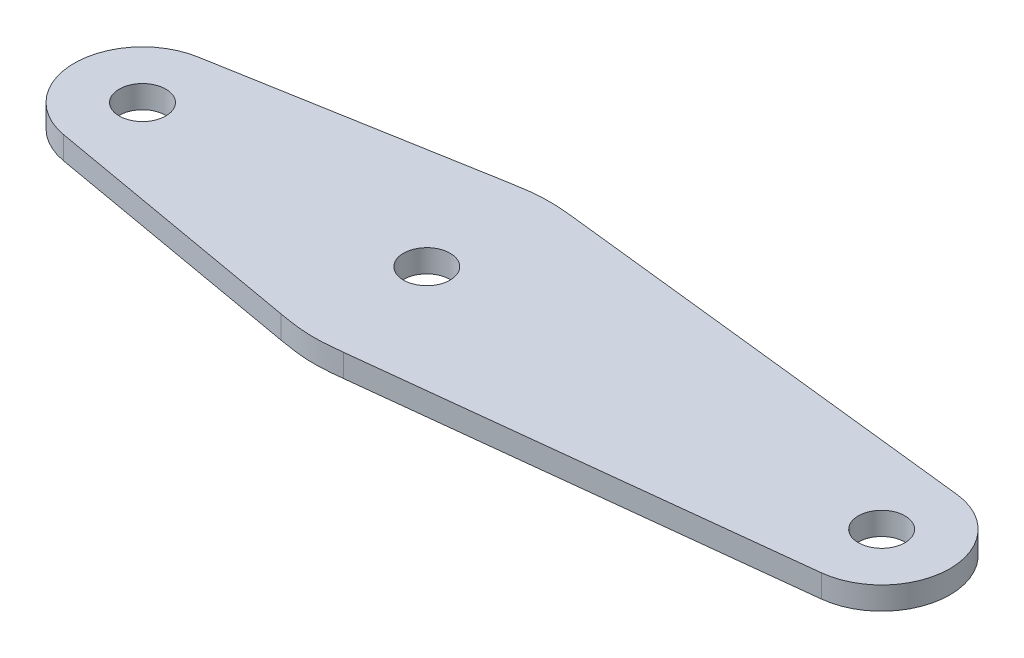
SolidWorks part; units mm, degrees
material "ABS"
ref_plane "前视基准面" through (0, 0, 0) normal (0, 0, 1) x (1, 0, 0)
ref_plane "上视基准面" through (0, 0, 0) normal (0, 1, 0) x (1, 0, 0)
ref_plane "右视基准面" through (0, 0, 0) normal (1, 0, 0) x (0, 0, -1)
other "Configuration Table"
sketch "草图1" plane through (0, 0, 0) normal (0, 1, 0) x (1, 0, 0)
  line L0 (-96.1987, 0) -> (0, 0) construction
  line L1 (0, 0) -> (50, 0) construction
  line L2 (50, 0) -> (130, 0) construction
  line L3 (-2.0835, 11.8178) -> (50, 21)
  line L4 (50, 21) -> (131.3306, 11.926)
  line L5 (-2.0835, -11.8178) -> (50, -21)
  line L6 (50, -21) -> (131.3306, -11.926)
  circle A0 centre (0, 0) radius 4.1
  circle A1 centre (50, 0) radius 4.1
  circle A2 centre (130, 0) radius 4.1
  arc A3 (-2.0835, -11.8178) -> (-2.0835, 11.8178) centre (0, 0) cw
  arc A4 (131.3306, 11.926) -> (131.3306, -11.926) centre (130, 0) cw
  dimension "D1" = 8.2
  dimension "D2" = 8.2
  dimension "D3" = 8.2
  dimension "D4" = 50
  dimension "D6" = 12
  dimension "D7" = 12
  dimension "D8" = 42
  dimension "D5" = 80
extrude "凸台-拉伸1" add sketch "草图1" along normal blind 4
fillet "圆角1" radius 40 2 edges at (50, 2, 21) (50, 2, -21) curvature continuous yes
